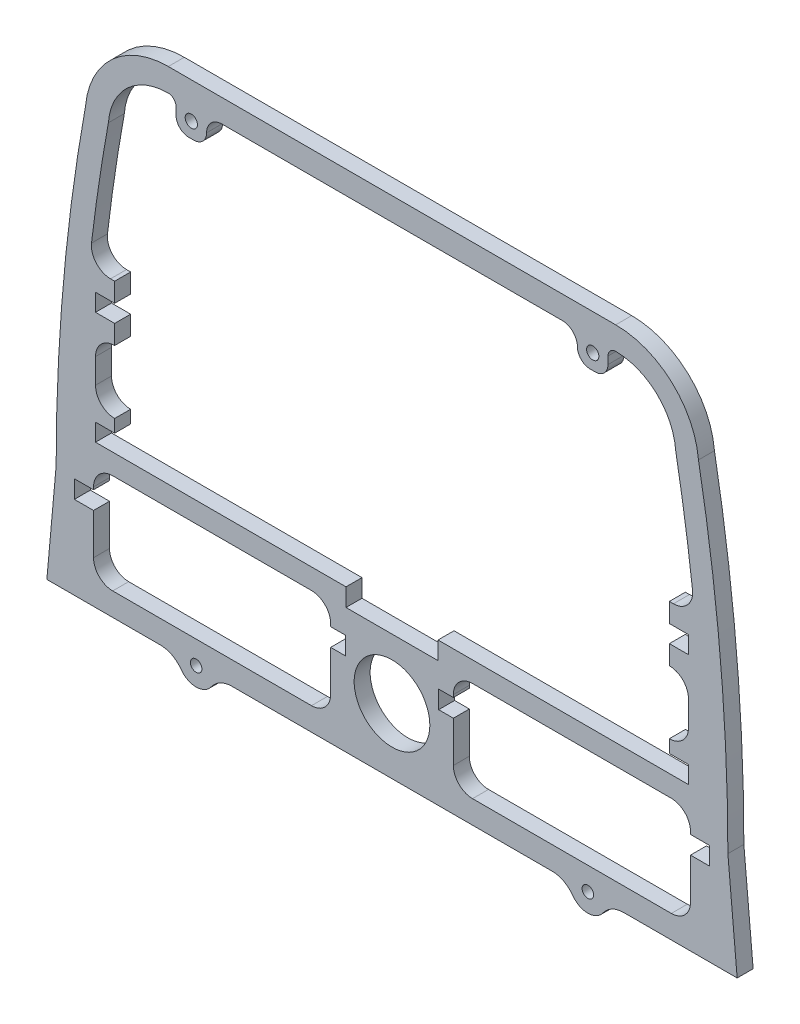
SolidWorks part; units mm, degrees
material "Delrin 2700 NC010, Low Viscosity Acetal Copolymer (SS)"
ref_plane "Front Plane" through (0, 0, 0) normal (0, 0, 1) x (1, 0, 0)
ref_plane "Top Plane" through (0, 0, 0) normal (0, 1, 0) x (1, 0, 0)
ref_plane "Right Plane" through (0, 0, 0) normal (1, 0, 0) x (0, 0, -1)
sketch "Sketch1" plane through (0, 0, 0) normal (0, 0, 1) x (1, 0, 0)
  line L0 (33.3676, -11.9888) -> (34.29, -22.225)
  line L1 (22.225, 27.94) -> (-22.225, 27.94)
  line L2 (-34.29, -22.225) -> (-30.4467, 20.4259) construction
  line L3 (-33.3676, -11.9888) -> (-33.3676, 14.6458) construction
  line L4 (-33.3676, -11.9888) -> (-34.29, -22.225)
  line L5 (16.9079, 25.654) -> (-16.9079, 25.654)
  line L6 (6.096, -13.97) -> (6.096, -19.939)
  line L7 (-29.6529, -19.939) -> (-6.096, -19.939)
  line L8 (-34.29, -22.225) -> (-21.299, -22.225)
  line L9 (-29.6529, -10.033) -> (-29.6529, -12.192)
  line L10 (18.4213, 24.1407) -> (18.4213, 24.1363)
  line L11 (19.6913, 22.8663) -> (20.1867, 22.8663)
  line L12 (21.4567, 24.1363) -> (21.4567, 24.8713)
  line L13 (-21.4567, 24.1363) -> (-21.4567, 24.8713)
  line L14 (-19.6913, 22.8663) -> (-20.1867, 22.8663)
  line L15 (-18.4213, 24.1407) -> (-18.4213, 24.1363)
  line L16 (29.4572, -8.001) -> (4.572, -8.001)
  line L17 (29.6529, -10.033) -> (6.096, -10.033)
  line L18 (0, 18.415) -> (0, -18.415) construction
  line L19 (-1007.9925, 0) -> (48992.0075, 0) construction
  line L20 (-6.096, -10.033) -> (-29.6529, -10.033)
  line L21 (19.939, 24.384) -> (21.4567, 24.384) construction
  line L22 (6.096, -19.939) -> (29.6529, -19.939)
  line L23 (-6.096, -10.033) -> (-6.096, -12.192)
  line L24 (5.9491, -2.2098) -> (59.5431, -2.2098) construction
  line L25 (5.9491, -2.2098) -> (5.9491, -11.9888) construction
  line L26 (3.4091, -11.9888) -> (-3.4091, -11.9888) construction
  line L27 (59.5431, -2.2098) -> (59.5431, -11.9888) construction
  line L28 (-31.7887, -19.939) -> (31.7887, -19.939) construction
  line L29 (22.225, 25.654) -> (-22.225, 25.654) construction
  line L30 (-6.096, -19.939) -> (-6.1666, -19.9899)
  line L31 (29.4572, -6.2738) -> (27.5522, -6.2738)
  line L32 (27.5522, -6.2738) -> (27.5522, -5.0038)
  line L33 (-29.6529, -12.192) -> (-31.5579, -12.192)
  line L34 (27.5522, -5.0038) -> (29.4572, -5.0038)
  line L35 (29.4572, 1.27) -> (27.5522, 1.27)
  line L36 (27.5522, 1.27) -> (27.5522, 3.175)
  line L37 (27.5522, 3.175) -> (29.4572, 3.175)
  line L38 (29.4572, 4.9022) -> (27.5522, 4.9022)
  line L39 (19.939, 24.384) -> (18.4213, 24.384) construction
  line L40 (27.5522, 4.9022) -> (27.5522, 6.8072)
  line L41 (27.5522, 6.8072) -> (30.0922, 6.8072)
  line L42 (19.939, 24.384) -> (19.939, 22.8663) construction
  line L43 (6.096, -10.033) -> (6.096, -12.192)
  line L44 (-29.4572, -6.2738) -> (-29.4572, -8.001)
  line L45 (-29.4572, -6.2738) -> (-27.5522, -6.2738)
  line L46 (-27.5522, -6.2738) -> (-27.5522, -5.0038)
  line L47 (-27.5522, -5.0038) -> (-29.4572, -5.0038)
  line L48 (-29.4572, 1.27) -> (-29.4572, -5.0038)
  line L49 (-29.4572, 1.27) -> (-27.5522, 1.27)
  line L50 (-27.5522, 1.27) -> (-27.5522, 3.175)
  line L51 (-27.5522, 3.175) -> (-29.4572, 3.175)
  line L52 (-29.4572, 4.9022) -> (-29.4572, 3.175)
  line L53 (-31.5579, -12.192) -> (-31.5579, -13.97)
  line L54 (-31.5579, -13.97) -> (-29.6529, -13.97)
  line L55 (-6.096, -12.192) -> (-4.6339, -12.192)
  line L56 (-4.6339, -12.192) -> (-4.6339, -13.97)
  line L57 (-4.6339, -13.97) -> (-6.096, -13.97)
  line L58 (-29.6529, -10.033) -> (-29.6529, -19.939) construction
  line L59 (-29.6529, -14.986) -> (-33.4249, -14.986) construction
  line L60 (-29.6529, -14.986) -> (-0.4824, -14.986) construction
  line L61 (-6.096, -13.97) -> (-6.096, -19.939)
  line L62 (-29.6529, -19.939) -> (-29.6529, -13.97)
  line L63 (29.6529, -19.939) -> (29.6529, -13.97)
  line L64 (-31.0816, -12.0913) -> (-31.7887, -19.939) construction
  line L65 (29.6529, -10.033) -> (29.6529, -12.192)
  line L66 (31.5579, -13.97) -> (29.6529, -13.97)
  line L67 (31.5579, -12.192) -> (31.5579, -13.97)
  line L68 (29.6529, -12.192) -> (31.5579, -12.192)
  line L69 (6.096, -12.192) -> (4.6339, -12.192)
  line L70 (4.6339, -12.192) -> (4.6339, -13.97)
  line L71 (4.6339, -13.97) -> (6.096, -13.97)
  line L72 (29.4572, 4.9022) -> (29.4572, 3.175)
  line L73 (31.0816, -12.0913) -> (31.7887, -19.939) construction
  line L74 (29.4572, 1.27) -> (29.4572, -5.0038)
  line L75 (29.4572, -6.2738) -> (29.4572, -8.001)
  line L76 (-29.4572, 4.9022) -> (-27.5522, 4.9022)
  line L77 (-27.5522, 4.9022) -> (-27.5522, 6.8072)
  line L78 (-27.5522, 6.8072) -> (-30.0922, 6.8072)
  line L79 (-17.616, -22.225) -> (17.616, -22.225)
  line L80 (21.299, -22.225) -> (34.29, -22.225)
  line L81 (-34.29, -22.225) -> (34.29, -22.225) construction
  line L82 (-4.572, -8.001) -> (-4.572, -9.779)
  line L83 (-4.572, -9.779) -> (0, -9.779)
  line L84 (0, -9.779) -> (4.572, -9.779)
  line L85 (4.572, -9.779) -> (4.572, -8.001)
  line L86 (-4.572, -8.001) -> (-29.4572, -8.001)
  arc A0 (22.225, 27.94) -> (30.4467, 20.4259) centre (22.225, 19.685) cw
  arc A1 (-22.225, 27.94) -> (-30.4467, 20.4259) centre (-22.225, 19.685) ccw
  arc A2 (33.3676, -11.9888) -> (30.4467, 20.4259) centre (-147.9525, -11.9888) ccw
  circle A3 centre (0, -15.748) radius 3.7592
  circle A4 centre (19.4575, -22.225) radius 0.5715
  arc A5 (-33.3676, -11.9888) -> (-30.4467, 20.4259) centre (147.9525, -11.9888) cw
  arc A6 (-17.616, -22.225) -> (-21.299, -22.225) centre (-19.4575, -22.225) cw
  arc A7 (17.616, -22.225) -> (21.299, -22.225) centre (19.4575, -22.225) ccw
  arc A8 (20.1867, 22.8663) -> (21.4567, 24.1363) centre (20.1867, 24.1363) ccw
  circle A9 centre (-19.939, 24.384) radius 0.6096
  circle A10 centre (19.939, 24.384) radius 0.6096
  arc A11 (18.4213, 24.1363) -> (19.6913, 22.8663) centre (19.6913, 24.1363) ccw
  circle A12 centre (-19.4575, -22.225) radius 0.5715
  arc A13 (18.4213, 24.1407) -> (16.9079, 25.654) centre (16.9079, 24.1407) ccw
  arc A14 (22.2416, 25.654) -> (21.4567, 24.8713) centre (22.2394, 24.8713) ccw
  arc A15 (-22.2416, 25.654) -> (-21.4567, 24.8713) centre (-22.2394, 24.8713) cw
  arc A16 (-20.1867, 22.8663) -> (-21.4567, 24.1363) centre (-20.1867, 24.1363) cw
  arc A17 (-18.4213, 24.1363) -> (-19.6913, 22.8663) centre (-19.6913, 24.1363) cw
  arc A18 (-22.2416, 25.654) -> (-28.1777, 20.1262) centre (-22.225, 19.685) ccw
  arc A19 (-18.4213, 24.1407) -> (-16.9079, 25.654) centre (-16.9079, 24.1407) cw
  arc A20 (31.0816, -12.0913) -> (31.0816, -11.9888) centre (-147.9525, -11.9888) ccw
  circle A21 centre (-19.4575, -22.225) radius 1.8415 construction
  arc A23 (22.2416, 25.654) -> (28.1777, 20.1262) centre (22.225, 19.685) cw
  arc A25 (-22.225, 25.654) -> (-28.1777, 20.1262) centre (-22.225, 19.685) ccw construction
  arc A26 (22.225, 25.654) -> (28.1777, 20.1262) centre (22.225, 19.685) cw construction
  arc A28 (-31.0816, -12.0913) -> (-28.1777, 20.1262) centre (147.9525, -11.9888) cw construction
  arc A30 (31.0816, -12.0913) -> (28.1777, 20.1262) centre (-147.9525, -11.9888) ccw construction
  arc A31 (30.0922, 6.8072) -> (28.1777, 20.1262) centre (-147.9525, -11.9888) ccw
  arc A33 (-30.0922, 6.8072) -> (-28.1777, 20.1262) centre (147.9525, -11.9888) cw
  point P0 (0, 0)
  point P1 (0, 27.94)
  point P31 (0, -11.9888)
  point P121 (-30.9018, -14.986)
  point P135 (-17.616, -22.225)
  dimension "D4" = 2.286
  dimension "D6" = 8.255
  dimension "D7" = 19.4575
  dimension "D8" = 50.165
  dimension "D9" = 15.748
  dimension "D5" = 1.2192
  dimension "D17" = 1.143
  dimension "D3" = 7.5184
  dimension "D18" = 1.27
  dimension "D19" = 1.27
  dimension "D26" = 11.176
  dimension "D28" = 0.7827
  dimension "D29" = 1.5133
  dimension "D32" = 1.905
  dimension "D2" = 44.45
  dimension "D10" = 1.27
  dimension "D11" = 1.27
  dimension "D12" = 68.58
  dimension "D13" = 19.939
  dimension "D14" = 22.225
  dimension "D15" = 53.594
  dimension "D16" = 9.779
  dimension "D20" = 6.096
  dimension "D21" = 11.938
  dimension "D22" = 2.032
  dimension "D23" = 1.7272
  dimension "D24" = 1.27
  dimension "D25" = 1.905
  dimension "D27" = 0.4954
  dimension "D30" = 1.905
  dimension "D31" = 1.7272
  dimension "D33" = 1.778
  dimension "D34" = 2.159
  dimension "D35" = 23.5569
  dimension "D36" = 26.924
  dimension "D37" = 1.905
  dimension "D38" = 2.54
  dimension "D39" = 1.778
  dimension "D40" = 9.144
extrude "Boss-Extrude1" add sketch "Sketch1" along normal blind 1.5875 contours L8 A12 A4 L0 A2 A0 L1 A1 A5 L4 L74 L16 A18 A15 L13 A16 L14 A17 L15 A19 L5 A13 L10 A11 L11 A8 L12 A14 A23 A20 L22 L43 L17 A10 A9 A3 L20 region at (32.9716, -17.1841, 0)
ref_axis "Axis1" through (0, -15.748, 0) along (0, 0, 1)
fillet "Fillet1" radius 1.905 8 edges at (-6.096, -10.033, 0.7937) (6.096, -10.033, 0.7937) (-6.096, -19.939, 0.7937) (-29.6529, -19.939, 0.7937) (-29.6529, -10.033, 0.7937) (6.096, -19.939, 0.7937) (29.6529, -19.939, 0.7937) (29.6529, -10.033, 0.7937)
fillet "Fillet2" radius 1.905 6 edges at (-29.4572, 1.27, 0.7937) (-29.4572, -5.0038, 0.7937) (-30.0922, 6.8072, 0.7937) (29.4572, -5.0038, 0.7937) (29.4572, 1.27, 0.7937) (30.0922, 6.8072, 0.7937)
fillet "Fillet3" radius 2.54 4 edges at (-17.616, -22.225, 0.7937) (-21.299, -22.225, 0.7937) (17.616, -22.225, 0.7937) (21.299, -22.225, 0.7937)
